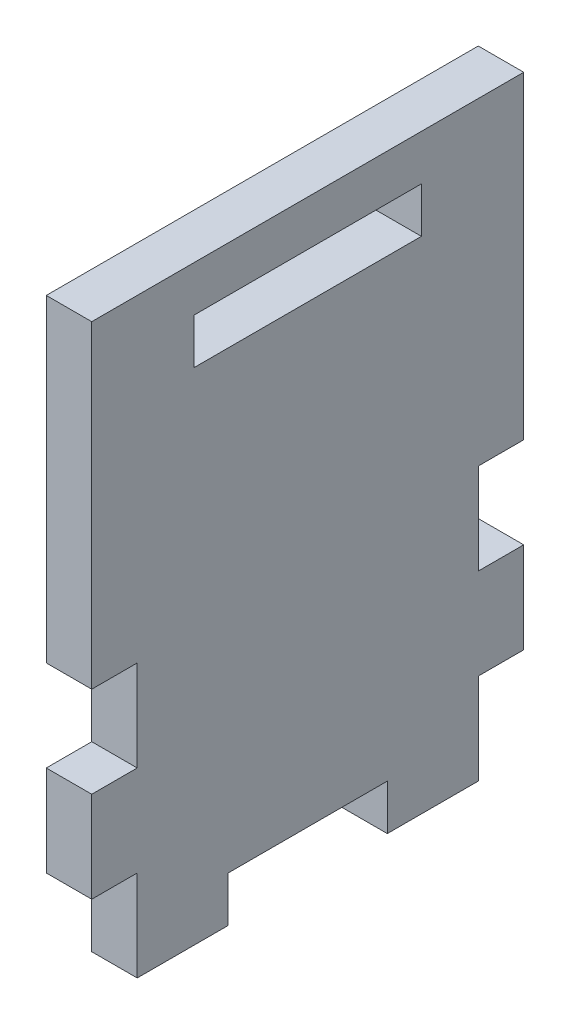
SolidWorks part; units mm, degrees
ref_plane "Plano frontal" through (0, 0, 0) normal (0, 0, 1) x (1, 0, 0)
ref_plane "Plano superior" through (0, 0, 0) normal (0, 1, 0) x (1, 0, 0)
ref_plane "Plano direito" through (0, 0, 0) normal (1, 0, 0) x (0, 0, -1)
sketch "ParedeEsboco" plane through (0, 0, 0) normal (1, 0, 0) x (0, 0, -1)
  line L0 (0, -19.5) -> (0, 19.5) construction
  line L6 (14.25, -13.5) -> (11.25, -13.5)
  line L7 (-7.5, 16.5) -> (7.5, 16.5)
  line L8 (-7.5, 16.5) -> (-7.5, 13.5)
  line L9 (-7.5, 13.5) -> (7.5, 13.5)
  line L10 (7.5, 16.5) -> (7.5, 13.5)
  line L11 (-14.25, 10.5) -> (14.25, 10.5) construction
  line L12 (-11.25, -19.5) -> (-11.25, -13.5)
  line L13 (-11.25, -13.5) -> (-14.25, -13.5)
  line L14 (-14.25, -13.5) -> (-14.25, -7.5)
  line L15 (-14.25, -7.5) -> (-11.25, -7.5)
  line L16 (-11.25, -7.5) -> (-11.25, -1.5)
  line L17 (-11.25, -1.5) -> (-14.25, -1.5)
  line L18 (-14.25, -1.5) -> (-14.25, 10.5)
  line L19 (-14.25, 10.5) -> (-14.25, 19.5)
  line L20 (14.25, 19.5) -> (14.25, 10.5)
  line L21 (14.25, 10.5) -> (14.25, -1.5)
  line L22 (14.25, -1.5) -> (11.25, -1.5)
  line L23 (11.25, -1.5) -> (11.25, -7.5)
  line L24 (11.25, -7.5) -> (14.25, -7.5)
  line L26 (-14.25, 19.5) -> (14.25, 19.5)
  line L27 (11.25, -13.5) -> (11.25, -19.5)
  line L28 (14.25, -13.5) -> (14.25, -7.5)
  line L29 (11.25, -19.5) -> (5.25, -19.5)
  line L30 (5.25, -19.5) -> (5.25, -16.5)
  line L31 (5.25, -16.5) -> (-5.25, -16.5)
  line L32 (-5.25, -16.5) -> (-5.25, -19.5)
  line L33 (-5.25, -19.5) -> (-11.25, -19.5)
  point P0 (0, 0)
  point P2 (0, 0)
  point P10 (0, 16.5)
  point P22 (0, 19.5)
  dimension "D1" = 28.5
  dimension "D2" = 39
  dimension "D3" = 3
  dimension "D4" = 3
  dimension "D5" = 15
  dimension "D6" = 3
  dimension "D7" = 6
  dimension "D8" = 6
  dimension "D9" = 6
  dimension "D10" = 9
  dimension "D11" = 3
  dimension "D12" = 6
  dimension "D13" = 6
  dimension "D14" = 6
  dimension "D15" = 6
  dimension "D16" = 3
extrude "Parede" add sketch "ParedeEsboco" along normal blind 3
